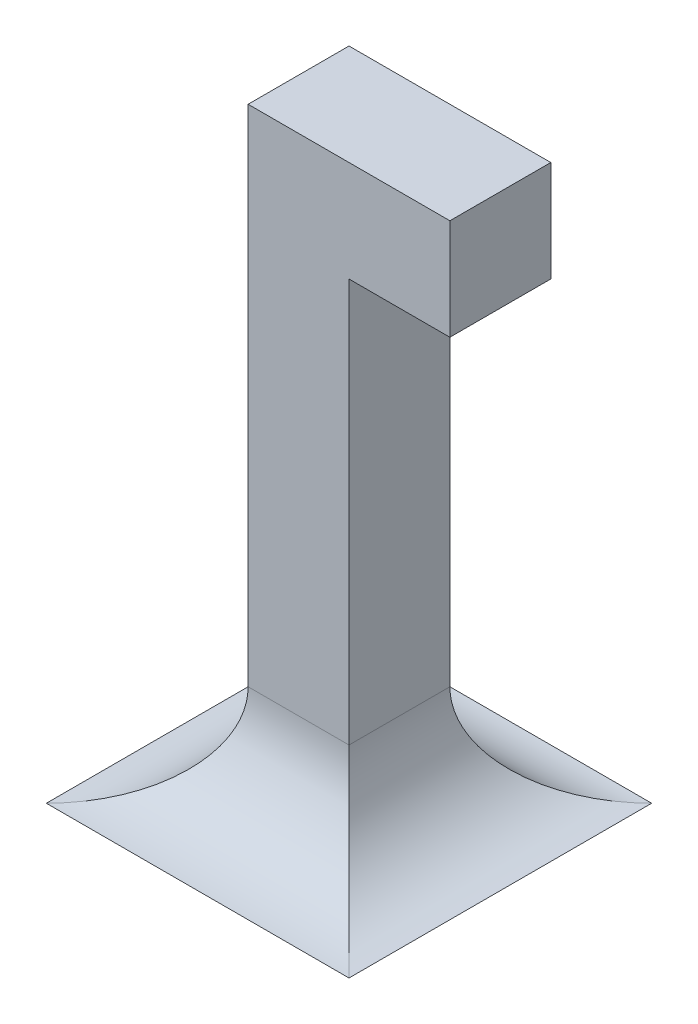
SolidWorks part; units mm, degrees
ref_plane "Front Plane" through (0, 0, 0) normal (0, 0, 1) x (1, 0, 0)
ref_plane "Top Plane" through (0, 0, 0) normal (0, 1, 0) x (1, 0, 0)
ref_plane "Right Plane" through (0, 0, 0) normal (1, 0, 0) x (0, 0, -1)
sketch "Sketch1" plane through (0, 0, 0) normal (0, 1, 0) x (1, 0, 0)
  line L0 (23.9959, -35) -> (56.9959, -35)
  line L4 (88.9959, -25) -> (88.9959, 25)
  line L5 (0, -39.6238) -> (0, 46.4731) construction
  line L6 (23.9959, 0) -> (23.9959, -28.538)
  line L7 (56.9959, -75) -> (88.9959, -75)
  line L8 (88.9959, -75) -> (88.9959, -25)
  line L10 (17.5, 25) -> (88.9959, 25)
  line L11 (73.9959, 41.1849) -> (73.9959, -116.2589) construction
  line L12 (23.9959, -28.538) -> (10.4959, -28.538)
  line L13 (10.4959, -28.538) -> (10.4959, -35)
  line L14 (10.4959, -35) -> (23.9959, -35)
  line L16 (17.5, 25) -> (-2.0041, 25)
  line L17 (-2.0041, 25) -> (-2.0041, 7.8405)
  line L19 (23.9959, 0) -> (23.9959, 7.8405)
  line L20 (23.9959, 7.8405) -> (-2.0041, 7.8405)
  line L21 (23.9959, 0) -> (73.9959, 0) construction
  line L22 (56.9959, -35) -> (56.9959, -75)
  circle A7 centre (51.4959, 0) radius 5
  circle A9 centre (73.9959, -60) radius 10.05
  circle A10 centre (5.147, 17.7557) radius 2.5 construction
  point P0 (0, 0)
  dimension "D5" = 100
  dimension "D4" = 10
  dimension "D8" = 20.1
  dimension "D13" = 5
  dimension "D2" = 13.5
  dimension "D6" = 91
  dimension "D9" = 15
  dimension "D10" = 50
  dimension "D11" = 32
extrude "Boss-Extrude1" add sketch "Sketch1" along normal blind 10
sketch "Sketch2" plane through (10.4959, 0, 0) normal (-1, 0, 0) x (0, 0, 1)
  line L0 (31.769, 0) -> (31.769, 10) construction
  line L1 (28.538, 0) -> (35, 0) construction
  line L2 (28.538, 5) -> (35, 5) construction
  line L3 (28.538, 10) -> (28.538, 0) construction
  line L5 (28.538, 10) -> (35, 10) construction
  circle A0 centre (31.769, 5) radius 1.25
  point P10 (31.769, 5)
  dimension "D1" = 2.5
extrude "Cut-Extrude1" cut sketch "Sketch2" against normal blind 10 contours A0
sketch "Sketch4" plane through (0, 10, 0) normal (0, 1, 0) x (1, 0, 0)
  line L2 (88.9959, 25) -> (-2.0041, 25) construction
  line L3 (-2.0041, 25) -> (-2.0041, 7.8405) construction
  circle A0 centre (6.4959, 16.5) radius 7.5
  dimension "D1" = 15
  dimension "D2" = 8.5
  dimension "D3" = 8.5
extrude "Boss-Extrude2" add sketch "Sketch4" along normal blind 30 draft 7 contours A0
sketch "Sketch5" plane through (0, 40, 0) normal (0, 1, 0) x (1, 0, 0)
  line L0 (-2.0041, 25) -> (-2.0041, 7.8405) construction
  line L1 (88.9959, 25) -> (-2.0041, 25) construction
  circle A0 centre (6.4959, 16.5) radius 1.25
  dimension "D1" = 8.5
  dimension "D2" = 8.5
  dimension "D3" = 2.5
extrude "Cut-Extrude2" cut sketch "Sketch5" against normal blind 10
fillet "Fillet1" radius 15 3 edges at (56.9959, 5, 35) (23.9959, 5, 28.538) (23.9959, 5, -7.8405)
sketch "Sketch6" plane through (0, 10, 0) normal (0, 1, 0) x (1, 0, 0)
  line L0 (88.9959, -75) -> (88.9959, 25) construction
  line L1 (73.9959, 20) -> (78.9959, 20)
  line L2 (73.9959, 20) -> (73.9959, 15)
  line L3 (73.9959, 15) -> (78.9959, 15)
  line L4 (78.9959, 20) -> (78.9959, 15)
  line L5 (73.9959, 20) -> (78.9959, 15) construction
  line L6 (73.9959, 15) -> (78.9959, 20) construction
  line L7 (88.9959, 25) -> (-2.0041, 25) construction
  point P0 (76.4959, 17.5)
  dimension "D1" = 5
  dimension "D2" = 5
  dimension "D3" = 10
  dimension "D4" = 5
extrude "Boss-Extrude3" add sketch "Sketch6" along normal blind 30
sketch "Sketch7" plane through (78.9959, 0, 0) normal (1, 0, 0) x (0, 0, -1)
  line L0 (20, 40) -> (20, 10) construction
  line L1 (15, 40) -> (20, 40)
  line L2 (15, 40) -> (15, 35)
  line L3 (15, 35) -> (20, 35)
  line L4 (20, 40) -> (20, 35)
  dimension "D1" = 5
extrude "Boss-Extrude4" add sketch "Sketch7" along normal blind 5
fillet "Fillet2" radius 5 4 edges at (76.4959, 10, -15) (73.9959, 10, -17.5) (76.4959, 10, -20) (78.9959, 10, -17.5)
sketch "Sketch8" plane through (88.9959, 0, 0) normal (1, 0, 0) x (0, 0, -1)
  line L1 (-75, 10) -> (25, 10)
  line L2 (-75, 10) -> (-75, 0)
  line L3 (-75, 0) -> (25, 0)
  line L4 (25, 10) -> (25, 0)
extrude "Cut-Extrude4" cut sketch "Sketch8" against normal blind 100
ref_plane "Plane1" through (0, 0, -20) normal (0, 0, 1) x (1, 0, 0)
